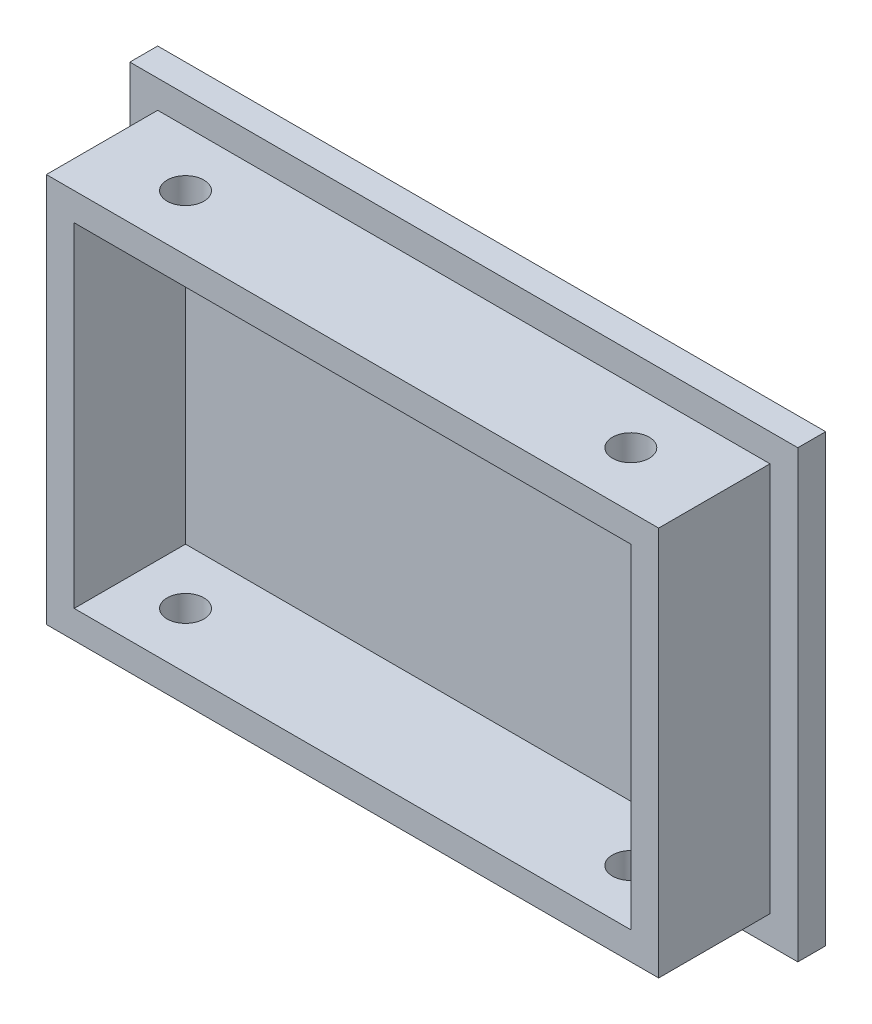
SolidWorks part; units mm, degrees
material "ABS"
ref_plane "Front Plane" through (0, 0, 0) normal (0, 0, 1) x (1, 0, 0)
ref_plane "Top Plane" through (0, 0, 0) normal (0, 1, 0) x (1, 0, 0)
ref_plane "Right Plane" through (0, 0, 0) normal (1, 0, 0) x (0, 0, -1)
sketch "Sketch1" plane through (0, 0, 0) normal (0, 0, 1) x (1, 0, 0)
  line L0 (29.9357, -19.05) -> (34.925, -22.225) construction
  line L1 (-34.925, 22.225) -> (34.925, 22.225)
  line L2 (-34.925, 22.225) -> (-34.925, -22.225)
  line L3 (-34.925, -22.225) -> (34.925, -22.225)
  line L4 (34.925, 22.225) -> (34.925, -22.225)
  line L5 (-34.925, 22.225) -> (-29.9357, 19.05) construction
  line L6 (-34.925, -22.225) -> (-29.9357, -19.05) construction
  line L7 (-31.75, 19.05) -> (31.75, 19.05)
  line L8 (-31.75, 19.05) -> (-31.75, -19.05)
  line L9 (-31.75, -19.05) -> (31.75, -19.05)
  line L10 (31.75, 19.05) -> (31.75, -19.05)
  line L11 (29.9357, 19.05) -> (34.925, 22.225) construction
  point P0 (0, 0)
  dimension "D1" = 69.85
  dimension "D2" = 44.45
  dimension "D3" = 3.175
  dimension "D4" = 3.175
  dimension "D5" = 3.175
  dimension "D6" = 3.175
extrude "Boss-Extrude1" add sketch "Sketch1" along normal blind 12.7
sketch "Sketch2" plane through (0, 22.225, 0) normal (0, 1, 0) x (1, 0, 0)
  line L0 (-34.925, -6.35) -> (-31.75, -6.35) construction
  line L1 (-34.925, -12.7) -> (-34.925, 0) construction
  line L2 (-31.75, -6.35) -> (-25.4, -6.35) construction
  line L3 (0, 0) -> (0, -12.7) construction
  line L4 (34.925, -12.7) -> (-34.925, -12.7) construction
  line L5 (34.925, -6.35) -> (31.75, -6.35) construction
  line L6 (31.75, -6.35) -> (25.4, -6.35) construction
  circle A0 centre (-25.4, -6.35) radius 2.0955
  circle A1 centre (25.4, -6.35) radius 2.0955
  dimension "D3" = 4.191
  dimension "D1" = 3.175
  dimension "D2" = 6.35
extrude "Cut-Extrude1" cut sketch "Sketch2" against normal up to surface (44.45 mm away) up to face at (0, -22.225, 6.35)
sketch "Sketch3" plane through (0, 0, 0) normal (0, 0, -1) x (-1, 0, 0)
  line L0 (-34.925, 22.225) -> (34.925, 22.225) construction
  line L1 (-38.1, 25.4) -> (38.1, 25.4)
  line L2 (-38.1, 25.4) -> (-38.1, -25.4)
  line L3 (-38.1, -25.4) -> (38.1, -25.4)
  line L4 (38.1, 25.4) -> (38.1, -25.4)
  line L5 (-38.1, 25.4) -> (38.1, -25.4) construction
  line L6 (-38.1, -25.4) -> (38.1, 25.4) construction
  line L8 (-34.925, -22.225) -> (-34.925, 22.225) construction
  line L9 (34.925, 22.225) -> (34.925, -22.225) construction
  point P0 (0, 0)
  dimension "D1" = 3.175
  dimension "D2" = 3.175
  dimension "D3" = 3.175
extrude "Boss-Extrude2" add sketch "Sketch3" along normal blind 3.175
